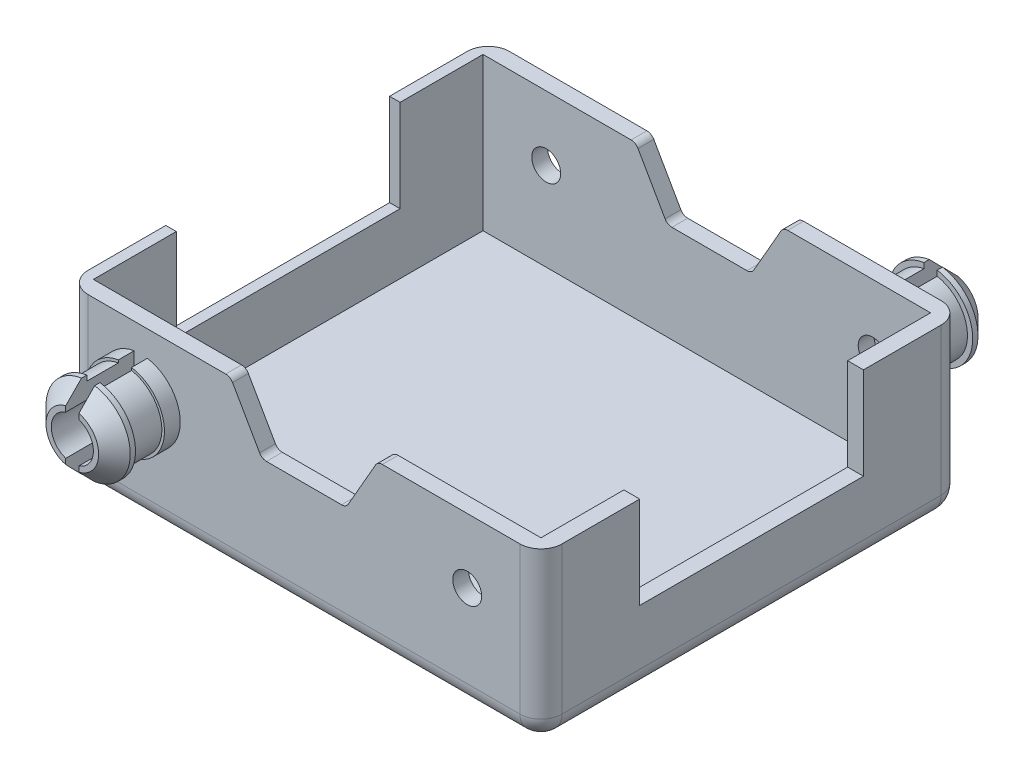
SolidWorks part; units mm, degrees
ref_plane "Front Plane" through (0, 0, 0) normal (0, 0, 1) x (1, 0, 0)
ref_plane "Top Plane" through (0, 0, 0) normal (0, 1, 0) x (1, 0, 0)
ref_plane "Right Plane" through (0, 0, 0) normal (1, 0, 0) x (0, 0, -1)
sketch "Sketch1" plane through (0, 0, 0) normal (0, 1, 0) x (1, 0, 0)
  line L1 (0, 0) -> (90, 0)
  line L2 (0, 0) -> (0, 80)
  line L3 (0, 80) -> (90, 80)
  line L4 (90, 0) -> (90, 80)
  dimension "D1" = 90
  dimension "D2" = 80
extrude "Boss-Extrude1" add sketch "Sketch1" along normal blind 32
shell "Shell1" thickness 3 removed face at (45, 32, -40)
fillet "Fillet1" radius 4 8 edges at (45, 0, 0) (90, 0, -40) (45, 0, -80) (0, 0, -40) (90, 16, -80) (90, 16, 0) (0, 16, -80) (0, 16, 0)
sketch "Sketch4" plane through (3, 0, 0) normal (1, 0, 0) x (0, 0, -1)
  line L4 (3, 3) -> (77, 3)
  line L5 (77, 3) -> (77, 32)
  line L6 (77, 32) -> (3, 32)
  line L7 (77, 3) -> (77, 32)
  line L8 (3, 3) -> (77, 3)
  line L10 (77, 32) -> (3, 32)
  line L12 (3, 32) -> (3, 3)
  line L13 (3, 32) -> (3, 3)
  dimension "D1" = 0
extrude "Cut-Extrude1" cut sketch "Sketch4" along normal blind 83.5 from offset 1 offset against normal yes
sketch "Sketch5" plane through (90, 0, 0) normal (1, 0, 0) x (0, 0, -1)
  line L0 (4, 32) -> (76, 32) construction
  line L1 (18.75, 32) -> (61.25, 32)
  line L2 (18.75, 32) -> (18.75, 14.5)
  line L3 (18.75, 14.5) -> (61.25, 14.5)
  line L4 (61.25, 32) -> (61.25, 14.5)
  line L6 (76, 0) -> (4, 0) construction
  line L7 (40, 4) -> (40, 46.3808) construction
  line L8 (4, 4) -> (76, 4) construction
  point P12 (40, 14.5)
  dimension "D1" = 42.5
  dimension "D2" = 14.5
extrude "Cut-Extrude2" cut sketch "Sketch5" against normal up to surface (90 mm away) up to face at (0, 18, -40)
sketch "Sketch6" plane through (0, 0, 0) normal (0, 0, 1) x (1, 0, 0)
  line L0 (4, 32) -> (86, 32) construction
  line L1 (37, 21.5) -> (53, 21.5)
  line L4 (53, 21.5) -> (53, 32) construction
  line L5 (37, 21.5) -> (45, 32) construction
  line L6 (45, 32) -> (53, 21.5) construction
  line L7 (53, 21.5) -> (59, 32)
  line L8 (37, 21.5) -> (31, 32)
  line L9 (31, 32) -> (59, 32)
  point P0 (45, 32)
  dimension "D1" = 8
  dimension "D2" = 14
  dimension "D3" = 14
  dimension "D4" = 10.5
extrude "Cut-Extrude3" cut sketch "Sketch6" against normal up to surface (80 mm away) up to face at (45, 18, -80)
fillet "Fillet2" radius 1.5 8 edges at (59, 32, -78.5) (53, 21.5, -78.5) (31, 32, -78.5) (37, 21.5, -78.5) (59, 32, -1.5) (53, 21.5, -1.5) (31, 32, -1.5) (37, 21.5, -1.5)
sketch "Sketch7" plane through (0, 0, 0) normal (0, 0, 1) x (1, 0, 0)
  line L1 (4, 4) -> (86, 4) construction
  line L2 (4, 32) -> (4, 4) construction
  line L3 (45, 4) -> (45, 37.0086) construction
  circle A0 centre (14, 19.75) radius 2.75
  circle A2 centre (76, 19.75) radius 2.75
  point P2 (14, 17)
  dimension "D1" = 5.5
  dimension "D2" = 13
  dimension "D4" = 10
extrude "Cut-Extrude4" cut sketch "Sketch7" against normal up to surface (80 mm away) up to face at (45, 23.8333, -80)
sketch "Sketch8" plane through (0, 0, 0) normal (0, 0, 1) x (1, 0, 0)
  line L0 (14, 19.75) -> (14, 30.7129) construction
  line L1 (12.75, 32) -> (12.75, 0) construction
  line L2 (4, 32) -> (30.1295, 32) construction
  line L3 (86, 0) -> (4, 0) construction
  line L4 (15.25, 32) -> (15.25, 0) construction
  circle A0 centre (14, 19.75) radius 8
  circle A2 centre (14, 19.75) radius 6
  circle A4 centre (14, 19.75) radius 5
  dimension "D1" = 16
  dimension "D2" = 3
  dimension "D3" = 1
  dimension "D4" = 1.25
  dimension "D5" = 2.5
sketch "Sketch9" plane through (0, 0, 0) normal (0, 0, 1) x (1, 0, 0)
  circle A0 centre (14, 19.75) radius 7.5
  circle A1 centre (14, 19.75) radius 2.75 construction
  circle A2 centre (14, 19.75) radius 2.75
  dimension "D1" = 15
extrude "Boss-Extrude3" add sketch "Sketch9" along normal blind 3
ref_axis "Axis1" through (14, 19.75, 0) along (0, 0, 1)
ref_plane "Plane1" through (14, 0, 0) normal (-1, 0, 0) x (0, 0, 1)
sketch "Sketch10" plane through (14, 0, 0) normal (-1, 0, 0) x (0, 0, 1)
  line L0 (0, 19.75) -> (33.8718, 19.75) construction
  line L1 (0, 32) -> (0, 0) construction
  line L2 (0, 19.75) -> (69.0457, 19.75) construction
  line L4 (13, 24.75) -> (10, 27.75)
  line L5 (10, 27.75) -> (9, 27.75)
  line L6 (9, 27.75) -> (9, 26.75)
  line L10 (3, 23.75) -> (13, 23.75)
  line L11 (13, 24.75) -> (13, 29.847) construction
  line L12 (10, 27.75) -> (15.9197, 21.8303) construction
  line L13 (13, 24.75) -> (13, 23.75)
  line L14 (9, 26.75) -> (3, 26.75)
  line L15 (3, 12.25) -> (3, 27.25) construction
  line L16 (3, 26.75) -> (3, 23.75)
  dimension "D1" = 1
  dimension "D2" = 1
  dimension "D3" = 4
  dimension "D4" = 135
  dimension "D5" = 1
  dimension "D6" = 8
  dimension "D7" = 10
revolve "Revolve1" add sketch "Sketch10" angle 360 about axis through (14, 19.75, 0) along (0, 0, 1)
sketch "Sketch11" plane through (0, 0, 0) normal (0, 0, 1) x (1, 0, 0)
  line L2 (12.75, 32) -> (12.75, 0) construction
  line L3 (12.75, 27.75) -> (15.25, 27.75)
  line L4 (15.25, 32) -> (15.25, 0) construction
  line L5 (15.25, 27.75) -> (15.25, 11.75)
  line L6 (15.25, 11.75) -> (12.75, 11.75)
  line L7 (12.75, 11.75) -> (12.75, 27.75)
extrude "Cut-Extrude5" cut sketch "Sketch11" along normal up to surface (13 mm away) up to face at (9, 19.75, 13)
ref_plane "Plane2" through (44.5, 0, 0) normal (-1, 0, 0) x (0, 0, 1)
ref_plane "Plane3" through (0, 0, -40) normal (0, 0, 1) x (1, 0, 0)
ref_plane "Plane4" through (42.25, 0, -42.25) normal (-0.7071, 0, 0.7071) x (0.7071, 0, 0.7071)
mirror "Mirror2" about plane through (44.5, 0, 0) normal (-1, 0, 0) of "Cut-Extrude5", "Revolve1", "Boss-Extrude3" second plane through (0, 0, -40) second plane normal (0, 0, 1)
sketch "Sketch12" plane through (0, 0, -80) normal (0, 0, -1) x (-1, 0, 0)
  line L0 (-4, 4) -> (-4, 32) construction
  line L1 (-29.2385, 30.4129) -> (-4, 30.4129)
  line L2 (-29.2385, 30.4129) -> (-29.2385, 7.9541)
  line L3 (-29.2385, 7.9541) -> (-4, 7.9541)
  line L4 (-4, 30.4129) -> (-4, 7.9541)
extrude "Cut-Extrude6" cut sketch "Sketch12" along normal up to surface (13 mm away) up to face at (11.125, 19.75, -93)
sketch "Sketch13" plane through (0, 0, 0) normal (0, 0, 1) x (1, 0, 0)
  line L0 (86, 4) -> (86, 32) construction
  line L1 (61.9909, 29.7891) -> (86, 29.7891)
  line L2 (61.9909, 29.7891) -> (61.9909, 10.4496)
  line L3 (61.9909, 10.4496) -> (86, 10.4496)
  line L4 (86, 29.7891) -> (86, 10.4496)
extrude "Cut-Extrude7" cut sketch "Sketch13" along normal up to surface (13 mm away)
